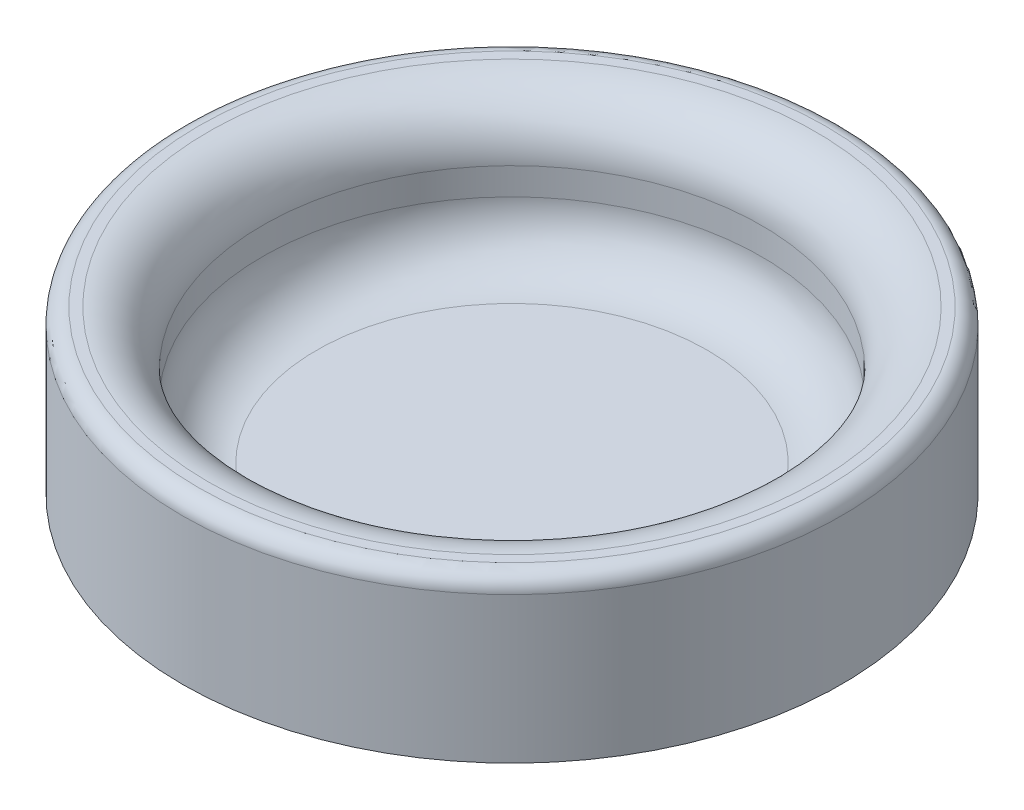
SolidWorks part; units mm, degrees
ref_plane "Front Plane" through (0, 0, 0) normal (0, 0, 1) x (1, 0, 0)
ref_plane "Top Plane" through (0, 0, 0) normal (0, 1, 0) x (1, 0, 0)
ref_plane "Right Plane" through (0, 0, 0) normal (1, 0, 0) x (0, 0, -1)
sketch "Sketch1" plane through (0, 0, 0) normal (0, 1, 0) x (1, 0, 0)
  circle A0 centre (-18.5586, 19.0375) radius 46.1321
  circle A1 centre (-18.5586, 19.0375) radius 60.958
extrude "Boss-Extrude1" add sketch "Sketch1" along normal blind 5 contours A1 A0 | A0 region at (-77.7924, 0, -19.0375)
extrude "Boss-Extrude2" add sketch "Sketch1<4>" along normal blind 30
sketch "Sketch1<4>" plane through (0, 0, 0) normal (0, 1, 0) x (1, 0, 0) same geometry as "Sketch1"
fillet "Fillet2" radius 10 1 edges at (-18.5586, 5, 27.0946)
fillet "Fillet3" radius 10 1 edges at (-18.5586, 30, 27.0946)
fillet "Fillet5" radius 3 1 edges at (-18.5586, 30, 41.9205)
